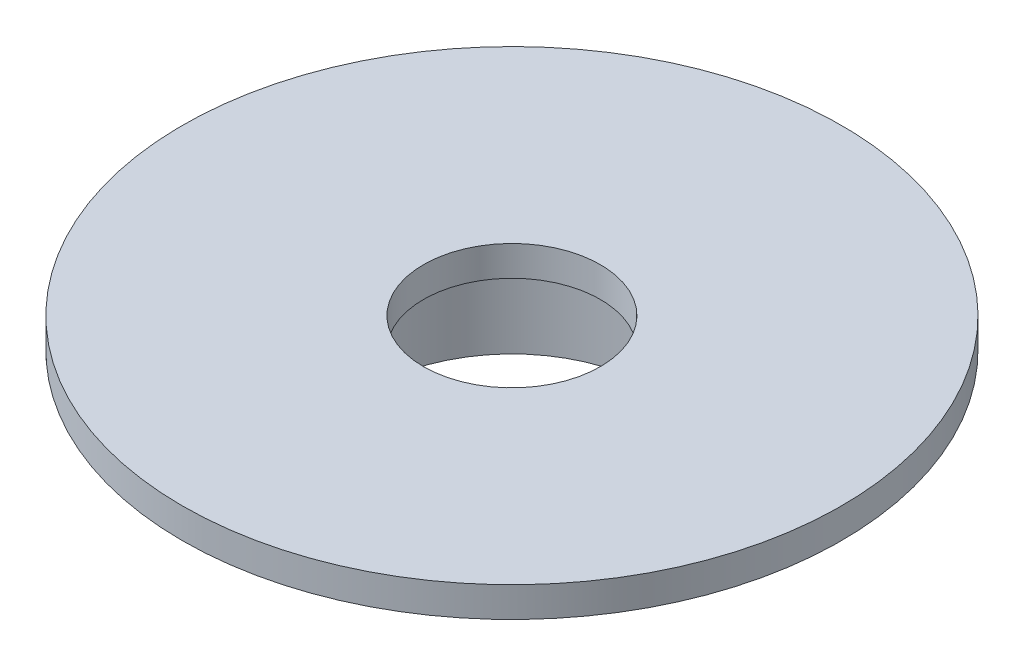
SolidWorks part; units mm, degrees
ref_plane "Plan de face" through (0, 0, 0) normal (0, 0, 1) x (1, 0, 0)
ref_plane "Plan de dessus" through (0, 0, 0) normal (0, 1, 0) x (1, 0, 0)
ref_plane "Plan de droite" through (0, 0, 0) normal (1, 0, 0) x (0, 0, -1)
sketch "Esquisse1" plane through (0, 0, 0) normal (0, 0, 1) x (1, 0, 0)
  line L0 (0, 35.6359) -> (0, -43.769) construction
  line L2 (4.4, 2.3519) -> (16.4, 2.3519)
  line L3 (16.4, 0.8519) -> (16.4, 2.3519)
  line L4 (7, -4.2481) -> (8.5, -4.2481)
  line L5 (8.5, -4.2481) -> (8.5, -2.7481)
  line L6 (8.5, -2.7481) -> (8, -2.7481)
  line L7 (8, -2.7481) -> (8, 0.8519)
  line L8 (4.4, 2.3519) -> (4.4, 0.8519)
  line L9 (4.4, 0.8519) -> (7, 0.8519)
  line L10 (7, 0.8519) -> (7, -4.2481)
  spline S0 degree 2 poles (8, 0.8519) (10.6678, 0.6769) (16.4, 0.8519) knots 0 0 0 1 1 1
  point P12 (8.5, -3.4981)
  dimension "D1" = 8.8
  dimension "D2" = 1.5
  dimension "D3" = 0.75
  dimension "D4" = 3.6
  dimension "D5" = 12
  dimension "D6" = 16
  dimension "D7" = 14
  dimension "D8" = 1.5
revolve "Révolution1" add sketch "Esquisse1" angle 360 about L0
ref_plane "Plan1" through (0, 0, 20) normal (0, 0, 1) x (1, 0, 0)
fillet "Congé4" radius 0.5 1 edges at (0, -2.7481, 8)
sketch "Esquisse2" plane through (0, 0, 20) normal (0, 0, 1) x (1, 0, 0)
  line L5 (16.4, 0.8519) -> (-16.4, 0.8519) construction
  line L6 (-0.75, 0.7399) -> (0.75, 0.7399)
  line L7 (-0.75, 0.7399) -> (-0.75, -4.4101)
  line L8 (0.75, 0.7399) -> (0.75, -4.4101)
  line L9 (-0.75, -4.4101) -> (0.75, -4.4101)
  point P4 (0, 0.8519)
  dimension "D1" = 0.75
  dimension "D2" = 0.75
  dimension "D3" = 5.15
extrude "Enlèv. mat.-Extru.1" cut sketch "Esquisse2" against normal blind 20
fillet "Congé2" radius 0.5 1 edges at (0, 0.8519, 7)
fillet "Congé3" radius 0.5 1 edges at (0, 0.8519, 8)
pattern_circular "Répétition circulaire1" count 2 over 360 about axis through (0, 35.6359, 0) along (0, 1, 0) of "Enlèv. mat.-Extru.1"
